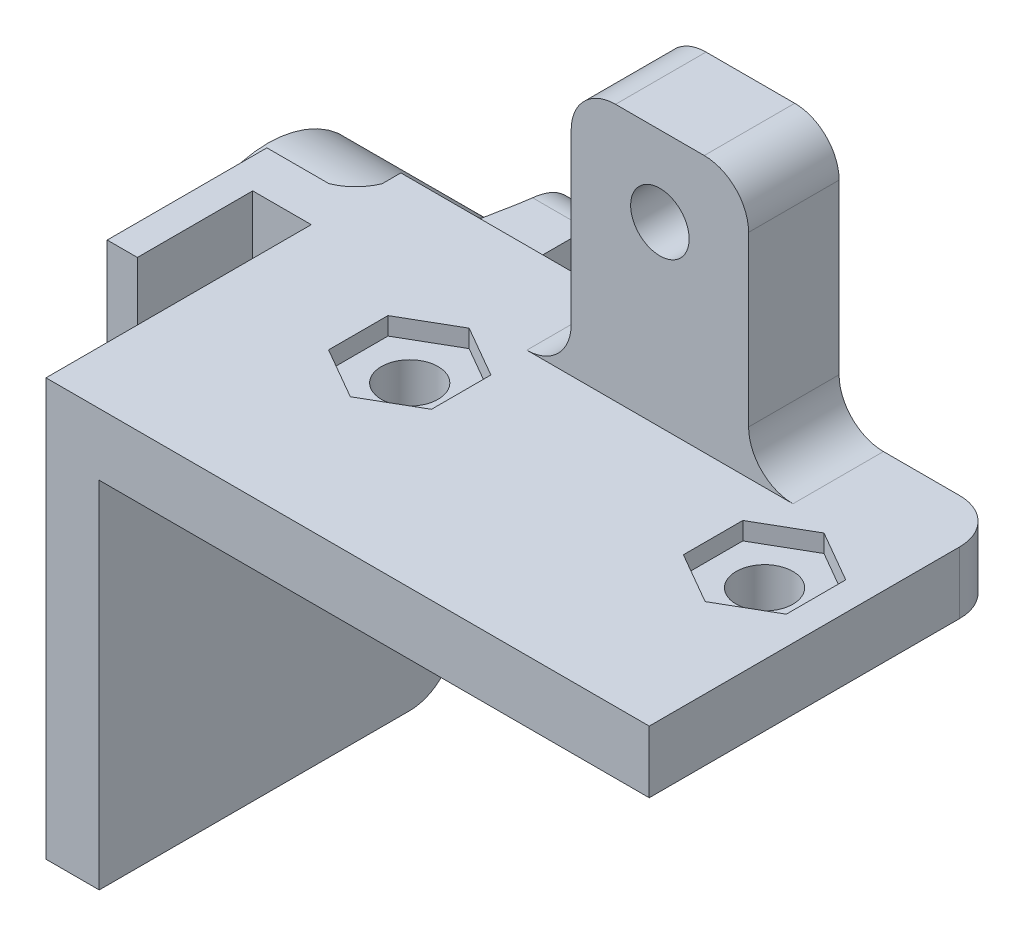
SolidWorks part; units mm, degrees
ref_plane "Alzado" through (0, 0, 0) normal (0, 0, 1) x (1, 0, 0)
ref_plane "Planta" through (0, 0, 0) normal (0, 1, 0) x (1, 0, 0)
ref_plane "Vista lateral" through (0, 0, 0) normal (1, 0, 0) x (0, 0, -1)
sketch "Croquis1" plane through (0, 0, 0) normal (0, 1, 0) x (1, 0, 0)
  line L1 (0, 0) -> (34, 0)
  line L2 (0, 0) -> (0, -20)
  line L3 (0, -20) -> (34, -20)
  line L4 (34, 0) -> (34, -20)
  dimension "D1" = 34
  dimension "D2" = 20
extrude "Saliente-Extruir1" add sketch "Croquis1" along normal blind 3.5
sketch "Croquis2" plane through (0, 3.5, 0) normal (0, 1, 0) x (1, 0, 0)
  line L0 (0, 0) -> (0, -20) construction
  line L1 (0, -20) -> (34, -20) construction
  circle A0 centre (9.5, -9) radius 1.6
  circle A1 centre (29.5, -9) radius 1.6
  dimension "D1" = 3.2
  dimension "D2" = 3.2
  dimension "D3" = 20
  dimension "D4" = 9.5
  dimension "D5" = 11
extrude "Cortar-Extruir1" cut sketch "Croquis2" against normal up to surface (3.5 mm away) up to face at (17, 0, 10)
sketch "Croquis3" plane through (0, 0, 0) normal (0, -1, 0) x (1, 0, 0)
  line L0 (0, 20) -> (34, 20) construction
  line L1 (0, 0) -> (3, 0)
  line L2 (0, 0) -> (0, 20)
  line L3 (0, 20) -> (3, 20)
  line L4 (3, 0) -> (3, 20)
  dimension "D1" = 3
extrude "Saliente-Extruir2" add sketch "Croquis3" along normal blind 20
sketch "Croquis4" plane through (0, 0, 0) normal (0, 0, -1) x (-1, 0, 0)
  line L0 (-3, -20) -> (-3, 0) construction
  line L1 (-3, -1.5) -> (0, -1.5)
  line L2 (-3, -1.5) -> (-3, -15.5)
  line L3 (-3, -15.5) -> (0, -15.5)
  line L4 (0, -1.5) -> (0, -15.5)
  line L5 (0, 3.5) -> (0, -20) construction
  line L6 (-34, 3.5) -> (0, 3.5) construction
  dimension "D1" = 14
  dimension "D2" = 5
extrude "Saliente-Extruir3" add sketch "Croquis4" along normal blind 10
sketch "Croquis5" plane through (0, 0, 0) normal (-1, 0, 0) x (0, 0, 1)
  line L0 (-10, -15.5) -> (0, -15.5) construction
  line L1 (0, 3.5) -> (0, -1.5) construction
  circle A0 centre (-3.5, -8.3) radius 6
  dimension "D1" = 12
  dimension "D2" = 7.2
  dimension "D3" = 3.5
extrude "Saliente-Extruir4" add sketch "Croquis5" along normal blind 11
sketch "Croquis6" plane through (-11, 0, 0) normal (-1, 0, 0) x (0, 0, 1)
  circle A0 centre (-3.5, -8.3) radius 1.5
  dimension "D1" = 3
extrude "Cortar-Extruir2" cut sketch "Croquis6" against normal up to surface (14 mm away) up to face at (3, -9.25, 2.5)
sketch "Croquis7" plane through (3, 0, 0) normal (1, 0, 0) x (0, 0, -1)
  line L0 (10, -1.5) -> (10, -15.5) construction
  line L1 (7.1, -12.9) -> (0.8, -12.9)
  line L2 (7.1, -12.9) -> (7.1, -4.6)
  line L3 (7.1, -4.6) -> (0.8, -4.6)
  line L4 (0.8, -12.9) -> (0.8, -4.6)
  line L5 (10, -15.5) -> (0, -15.5) construction
  dimension "D1" = 8.3
  dimension "D2" = 6.3
  dimension "D3" = 2.9
  dimension "D4" = 2.6
extrude "Cortar-Extruir3" cut sketch "Croquis7" against normal blind 6.4
sketch "Croquis8" plane through (-11, 0, 0) normal (-1, 0, 0) x (0, 0, 1)
  circle A0 centre (-3.5, -8.3) radius 4.2
  dimension "D1" = 8.4
extrude "Cortar-Extruir4" cut sketch "Croquis8" against normal blind 6.3
fillet "Redondeo1" radius 1 1 edges at (-3.4, -8.3, -5)
sketch "Croquis9" plane through (0, 0, 0) normal (-1, 0, 0) x (0, 0, 1)
  line L0 (20, -20) -> (0, -20) construction
  line L1 (2.55, -20) -> (11.55, -20)
  line L2 (2.55, -20) -> (2.55, 3.5)
  line L3 (2.55, 3.5) -> (11.55, 3.5)
  line L4 (11.55, -20) -> (11.55, 3.5)
  line L5 (0, 3.5) -> (20, 3.5) construction
  line L6 (0, 3.5) -> (0, -1.5) construction
  dimension "D1" = 9
  dimension "D2" = 2.55
extrude "Saliente-Extruir7" add sketch "Croquis9" along normal blind 5
sketch "Croquis10" plane through (0, 0, 11.55) normal (0, 0, 1) x (1, 0, 0)
  line L5 (-5, -20) -> (0, -20) construction
  line L6 (0, 3.5) -> (-3.3, 3.5)
  line L7 (0, 3.5) -> (0, -20)
  line L8 (0, -20) -> (-3.3, -20)
  line L9 (-3.3, 3.5) -> (-3.3, -20)
  dimension "D1" = 3.3
extrude "Cortar-Extruir5" cut sketch "Croquis10" against normal blind 6.5
sketch "Croquis11" plane through (0, 3.5, 0) normal (0, 1, 0) x (1, 0, 0)
  line L0 (34, 0) -> (0, 0) construction
  line L1 (24.7, 0) -> (14.7, 0)
  line L2 (24.7, 0) -> (24.7, -5.1)
  line L3 (24.7, -5.1) -> (14.7, -5.1)
  line L4 (14.7, 0) -> (14.7, -5.1)
  line L5 (34, -20) -> (34, 0) construction
  dimension "D1" = 10
  dimension "D2" = 5.1
  dimension "D3" = 9.3
extrude "Saliente-Extruir8" add sketch "Croquis11" along normal blind 14.5
sketch "Croquis12" plane through (0, 0, 0) normal (0, 0, -1) x (-1, 0, 0)
  line L0 (-24.7, 18) -> (-24.7, 3.5) construction
  line L1 (-34, 3.5) -> (-24.7, 3.5) construction
  circle A0 centre (-19.7, 13.5) radius 1.65
  dimension "D2" = 3.3
  dimension "D1" = 5
  dimension "D3" = 10
extrude "Cortar-Extruir6" cut sketch "Croquis12" against normal up to surface (5.1 mm away) up to face at (19.7, 10.75, 5.1)
sketch "Croquis13" plane through (0, 0, 0) normal (0, 0, -1) x (-1, 0, 0)
  circle A0 centre (-19.7, 13.5) radius 3
  dimension "D1" = 6
extrude "Cortar-Extruir7" cut sketch "Croquis13" against normal blind 2.6
sketch "Croquis15" plane through (0, 3.5, 0) normal (0, 1, 0) x (1, 0, 0)
  line L1 (9.5, -5.6514) -> (6.6, -7.3257)
  line L2 (6.6, -7.3257) -> (6.6, -10.6743)
  line L3 (6.6, -10.6743) -> (9.5, -12.3486)
  line L4 (9.5, -12.3486) -> (12.4, -10.6743)
  line L5 (12.4, -10.6743) -> (12.4, -7.3257)
  line L6 (12.4, -7.3257) -> (9.5, -5.6514)
  line L7 (29.5, -5.6514) -> (26.6, -7.3257)
  line L8 (26.6, -7.3257) -> (26.6, -10.6743)
  line L9 (26.6, -10.6743) -> (29.5, -12.3486)
  line L10 (29.5, -12.3486) -> (32.4, -10.6743)
  line L11 (32.4, -10.6743) -> (32.4, -7.3257)
  line L12 (32.4, -7.3257) -> (29.5, -5.6514)
  circle A0 centre (9.5, -9) radius 2.9 construction
  circle A1 centre (29.5, -9) radius 2.9 construction
  dimension "D1" = 5.8
  dimension "D2" = 5.8
extrude "Cortar-Extruir9" cut sketch "Croquis15" against normal blind 1
fillet "Redondeo3" radius 2.5 2 edges at (1.5, -15.5, -10) (1.5, -1.5, -10)
fillet "Redondeo5" radius 2.5 1 edges at (0, -8.3, -9.5)
sketch "Croquis16" plane through (0, -20, 0) normal (0, -1, 0) x (1, 0, 0)
  line L0 (-5, 2.55) -> (0, 2.55) construction
  line L2 (0, 2.55) -> (0, 0) construction
  line L3 (0, 1.05) -> (0, 2.55)
  line L4 (0, 2.55) -> (-1.5, 2.55)
  arc A0 (-1.5, 2.55) -> (0, 1.05) centre (-2.5583, -0.0083) cw
  dimension "D1" = 1.5
  dimension "D2" = 1.5
extrude "Saliente-Extruir9" add sketch "Croquis16" against normal up to surface (23.5 mm away) up to face at (9.5, 3.5, 9)
fillet "Redondeo6" radius 2.5 6 edges at (14.7, 3.5, 2.55) (24.7, 3.5, 2.55) (24.7, 18, 2.55) (14.7, 18, 2.55) (1.5, -20, 0) (34, 1.75, 0)
